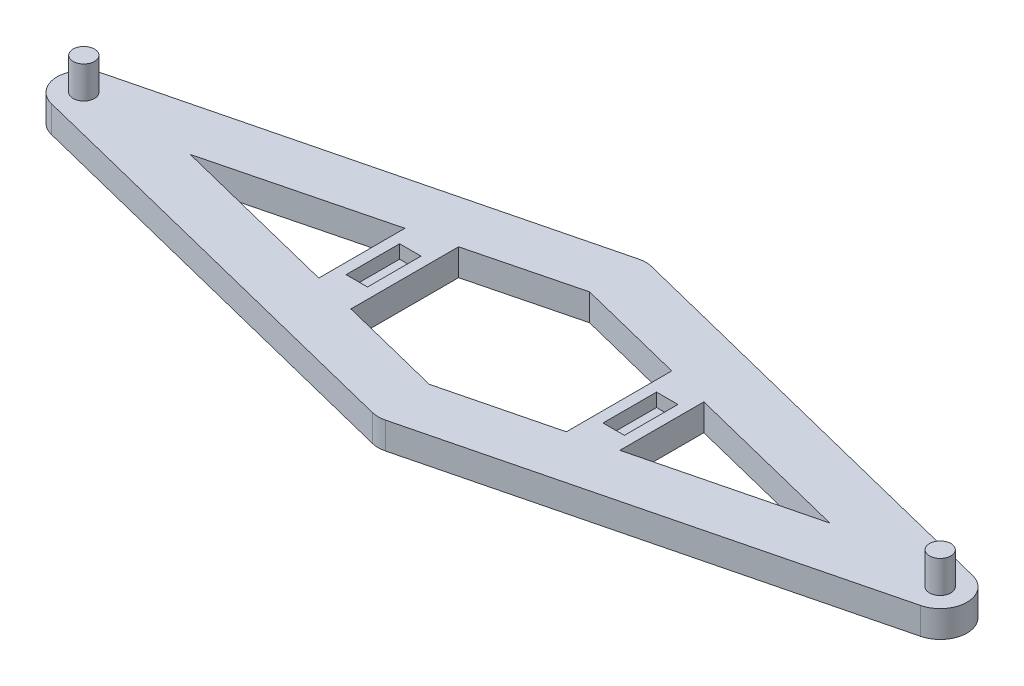
SolidWorks part; units mm, degrees
ref_plane "Front Plane" through (0, 0, 0) normal (0, 0, 1) x (1, 0, 0)
ref_plane "Top Plane" through (0, 0, 0) normal (0, 1, 0) x (1, 0, 0)
ref_plane "Right Plane" through (0, 0, 0) normal (1, 0, 0) x (0, 0, -1)
sketch "Base" plane through (0, 0, 0) normal (0, 1, 0) x (1, 0, 0)
  line L0 (-51.5701, 3.0802) -> (-0.7701, 15.7802)
  line L5 (-0.3074, -9.5041) -> (37.7091, 0)
  line L7 (0.7701, 15.7802) -> (51.5701, 3.0802)
  line L8 (-51.5701, -3.0802) -> (-0.7701, -15.7802)
  line L9 (51.5701, -3.0802) -> (0.7701, -15.7802)
  line L10 (-38.1111, -0.0652) -> (-0.2945, 9.5009)
  line L11 (-0.2945, 9.5009) -> (37.7091, 0)
  line L13 (-0.3074, -9.5041) -> (-38.1111, -0.0652)
  arc A0 (-51.5701, 3.0802) -> (-51.5701, -3.0802) centre (-50.8, 0) ccw
  arc A1 (0.7701, 15.7802) -> (-0.7701, 15.7802) centre (0, 12.7) ccw
  arc A2 (51.5701, -3.0802) -> (51.5701, 3.0802) centre (50.8, 0) ccw
  arc A3 (-0.7701, -15.7802) -> (0.7701, -15.7802) centre (0, -12.7) ccw
  circle A4 centre (-50.8, 0) radius 1.27
  circle A5 centre (50.8, 0) radius 1.27
  point P0 (0, 0)
  point P3 (-38.1111, -0.0652)
  dimension "D3" = 6.35
  dimension "D6" = 6.35
  dimension "D1" = 2.54
  dimension "D2" = 2.54
sketch "Sketch2" plane through (0, 0, 0) normal (0, 1, 0) x (1, 0, 0)
  line L0 (-51.5701, 3.0802) -> (-0.7701, 15.7802)
  line L1 (0.7701, 15.7802) -> (51.5701, 3.0802)
  line L2 (-51.5701, -3.0802) -> (-0.7701, -15.7802)
  line L3 (51.5701, -3.0802) -> (0.7701, -15.7802)
  line L4 (37.7091, 0) -> (-0.3074, -9.5041)
  line L5 (-0.3074, -9.5041) -> (-38.1111, -0.0652)
  line L6 (-38.1111, -0.0652) -> (-0.2945, 9.5009)
  line L7 (-0.2945, 9.5009) -> (37.7091, 0)
  arc A0 (-51.5701, 3.0802) -> (-51.5701, -3.0802) centre (-50.8, 0) ccw
  arc A1 (0.7701, 15.7802) -> (-0.7701, 15.7802) centre (0, 12.7) ccw
  arc A2 (51.5701, -3.0802) -> (51.5701, 3.0802) centre (50.8, 0) ccw
  arc A3 (-0.7701, -15.7802) -> (0.7701, -15.7802) centre (0, -12.7) ccw
extrude "Boss-Extrude1" add sketch "Sketch2" along normal blind 3.175
sketch "Sketch4" plane through (0, 3.175, 0) normal (0, 1, 0) x (1, 0, 0)
  line L0 (0, 12.7) -> (-50.8, 0)
  line L1 (-50.8, 0) -> (0, -12.7)
  line L2 (0, -12.7) -> (50.8, 0)
  line L3 (50.8, 0) -> (0, 12.7)
  line L4 (-17.78, 8.255) -> (-17.78, -8.255)
  line L5 (17.78, -8.255) -> (17.78, 8.255)
  line L14 (17.78, -8.255) -> (17.78, 8.255)
  line L19 (17.78, -8.255) -> (12.7, -8.255)
  line L20 (17.78, 8.255) -> (12.7, 8.255)
  line L21 (12.7, -8.255) -> (12.7, 8.255)
  line L22 (-17.78, -8.255) -> (-17.78, 8.255)
  line L23 (-17.78, -8.255) -> (-12.7, -8.255)
  line L24 (-17.78, 8.255) -> (-12.7, 8.255)
  line L25 (-12.7, -8.255) -> (-12.7, 8.255)
  circle A0 centre (-50.8, 0) radius 1.27
  circle A1 centre (50.8, 0) radius 1.27
  circle A4 centre (0, 0) radius 12.7
  point P9 (-17.78, 8.255)
  point P10 (17.78, 8.255)
  point P12 (17.78, -8.255)
  point P15 (-17.78, -8.255)
  dimension "D1" = 2.54
  dimension "D2" = 2.54
  dimension "D3" = 17.78
  dimension "D4" = 17.78
  dimension "D5" = 17.78
  dimension "D7" = 5.08
  dimension "D6" = 17.78
  dimension "D8" = 5.08
sketch "Sketch5" plane through (0, 3.175, 0) normal (0, 1, 0) x (1, 0, 0)
  circle A0 centre (-50.8, 0) radius 1.27
extrude "Boss-Extrude2" add sketch "Sketch5" along normal blind 3.81
sketch "Sketch6" plane through (0, 3.175, 0) normal (0, 1, 0) x (1, 0, 0)
  circle A0 centre (50.8, 0) radius 1.27
extrude "Boss-Extrude3" add sketch "Sketch6" along normal blind 3.81
sketch "Sketch10" plane through (0, 3.175, 0) normal (0, 1, 0) x (1, 0, 0)
  line L0 (-17.78, 8.255) -> (-17.78, -8.255)
  line L1 (17.78, -8.255) -> (17.78, 8.255)
  line L2 (17.78, -8.255) -> (12.7, -8.255)
  line L3 (17.78, 8.255) -> (12.7, 8.255)
  line L4 (12.7, -8.255) -> (12.7, 8.255)
  line L5 (-17.78, -8.255) -> (-12.7, -8.255)
  line L6 (-17.78, 8.255) -> (-12.7, 8.255)
  line L7 (-12.7, -8.255) -> (-12.7, 8.255)
extrude "Boss-Extrude6" add sketch "Sketch10" against normal up to surface (3.175 mm away) up to plane "Top Plane"
sketch "Sketch11" plane through (0, 3.175, 0) normal (0, 1, 0) x (1, 0, 0)
  line L0 (-15.24, 8.255) -> (-15.24, -8.255)
  line L1 (-17.78, 8.255) -> (-12.7, 8.255) construction
  line L2 (-17.78, -8.255) -> (-12.7, -8.255) construction
  line L3 (15.24, 8.255) -> (15.24, -8.255)
  line L4 (17.78, 8.255) -> (12.7, 8.255) construction
  line L5 (17.78, -8.255) -> (12.7, -8.255) construction
  line L7 (-16.51, -3.175) -> (-13.97, -3.175)
  line L8 (-16.51, -3.175) -> (-16.51, 3.175)
  line L9 (-16.51, 3.175) -> (-13.97, 3.175)
  line L10 (-13.97, -3.175) -> (-13.97, 3.175)
  line L11 (-16.51, -3.175) -> (-13.97, 3.175) construction
  line L12 (-16.51, 3.175) -> (-13.97, -3.175) construction
  line L13 (13.97, -3.175) -> (16.51, -3.175)
  line L14 (13.97, -3.175) -> (13.97, 3.175)
  line L15 (13.97, 3.175) -> (16.51, 3.175)
  line L16 (16.51, -3.175) -> (16.51, 3.175)
  line L17 (13.97, -3.175) -> (16.51, 3.175) construction
  line L18 (13.97, 3.175) -> (16.51, -3.175) construction
  point P12 (-15.24, 0)
  point P17 (15.24, 0)
  dimension "D1" = 2.54
  dimension "D2" = 6.35
  dimension "D3" = 2.54
  dimension "D4" = 6.35
sketch "Sketch13" plane through (0, 3.175, 0) normal (0, 1, 0) x (1, 0, 0)
  line L0 (-16.51, -3.175) -> (-13.97, -3.175)
  line L1 (-16.51, -3.175) -> (-16.51, 3.175)
  line L2 (-16.51, 3.175) -> (-13.97, 3.175)
  line L3 (-13.97, -3.175) -> (-13.97, 3.175)
  line L4 (13.97, -3.175) -> (16.51, -3.175)
  line L5 (13.97, -3.175) -> (13.97, 3.175)
  line L6 (13.97, 3.175) -> (16.51, 3.175)
  line L7 (16.51, -3.175) -> (16.51, 3.175)
extrude "Cut-Extrude1" cut sketch "Sketch13" against normal blind 1.5875
